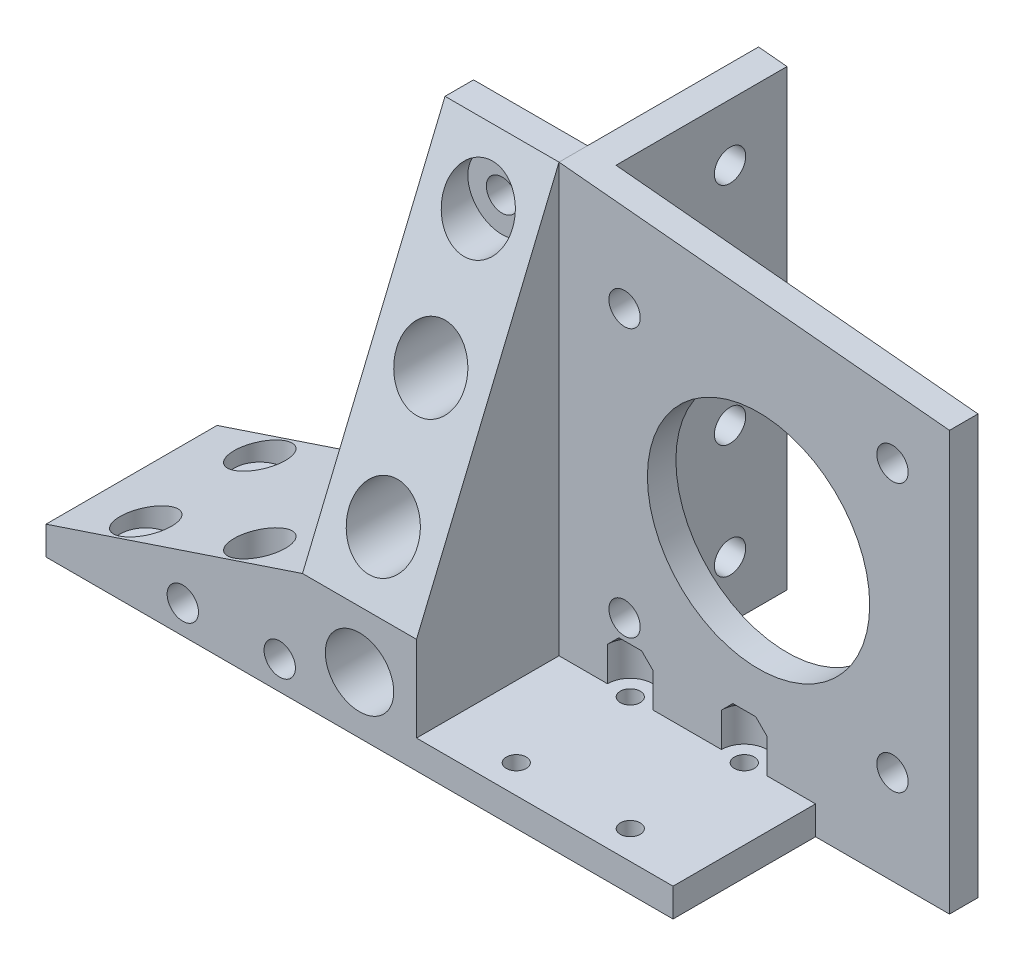
SolidWorks part; units mm, degrees
ref_plane "Plan de face" through (0, 0, 0) normal (0, 0, 1) x (1, 0, 0)
ref_plane "Plan de dessus" through (0, 0, 0) normal (0, 1, 0) x (1, 0, 0)
ref_plane "Plan de droite" through (0, 0, 0) normal (1, 0, 0) x (0, 0, -1)
sketch "Esquisse1" plane through (0, 0, 0) normal (0, 0, 1) x (1, 0, 0)
  line L1 (-9.5845, 32.7642) -> (10.4155, 32.7642)
  line L2 (-9.5845, 32.7642) -> (-9.5845, -47.2358)
  line L3 (-9.5845, -47.2358) -> (10.4155, -47.2358)
  line L4 (10.4155, 32.7642) -> (10.4155, -47.2358)
  circle A0 centre (0.4155, 22.7642) radius 2.75
  circle A1 centre (0.4155, -17.2358) radius 2.75
  circle A2 centre (0.4155, 2.7642) radius 2.75
  circle A3 centre (0.4155, -37.2358) radius 2.75
  point P13 (0.4155, -47.2358)
  dimension "D3" = 5.5
  dimension "D1" = 20
  dimension "D2" = 80
  dimension "D4" = 10
  dimension "D5" = 20
  dimension "D6" = 10
  dimension "D7" = 20
extrude "Boss.-Extru.1" add sketch "Esquisse1" along normal blind 5
sketch "Esquisse3" plane through (0, 0, 5) normal (0, 0, 1) x (1, 0, 0)
  line L0 (-9.5845, -47.2358) -> (-54.5845, -47.2358)
  line L1 (-54.5845, -47.2358) -> (-54.5845, -42.2358)
  line L2 (-54.5845, -42.2358) -> (-9.5845, -27.2358)
  line L3 (-9.5845, 32.7642) -> (-9.5845, -47.2358) construction
  line L4 (-9.5845, -27.2358) -> (-9.5845, -47.2358)
  line L5 (10.4155, -47.2358) -> (55.4155, -47.2358)
  line L6 (55.4155, -47.2358) -> (55.4155, -42.2358)
  line L7 (55.4155, -42.2358) -> (10.4155, -42.2358)
  line L8 (10.4155, -47.2358) -> (10.4155, 32.7642) construction
  line L9 (10.4155, -42.2358) -> (10.4155, -47.2358)
  dimension "D1" = 5
  dimension "D2" = 45
  dimension "D3" = 20
extrude "Boss.-Extru.2" add sketch "Esquisse3" against normal blind 5
sketch "Esquisse4" plane through (0, 0, 5) normal (0, 0, 1) x (1, 0, 0)
  line L0 (55.4155, -47.2358) -> (55.4155, -42.2358) construction
  line L1 (55.4155, -42.2358) -> (10.4155, -42.2358) construction
  line L2 (-9.5845, -27.2358) -> (-54.5845, -42.2358) construction
  line L3 (-54.5845, -42.2358) -> (-54.5845, -47.2358) construction
  line L4 (-54.5845, -47.2358) -> (55.4155, -47.2358) construction
  line L5 (55.4155, -47.2358) -> (55.4155, -42.2358)
  line L6 (55.4155, -42.2358) -> (10.4155, -42.2358)
  line L7 (-9.5845, -27.2358) -> (-54.5845, -42.2358)
  line L8 (-54.5845, -42.2358) -> (-54.5845, -47.2358)
  line L9 (-54.5845, -47.2358) -> (55.4155, -47.2358)
  line L11 (-9.5845, -27.2358) -> (10.4155, -27.2358)
  line L12 (10.4155, -42.2358) -> (10.4155, 32.7642) construction
  line L13 (10.4155, -27.2358) -> (10.4155, -42.2358)
  circle A0 centre (0.4155, -37.2358) radius 2.75 construction
  circle A1 centre (0.4155, -37.2358) radius 2.75
extrude "Boss.-Extru.3" add sketch "Esquisse4" along normal blind 25
sketch "Esquisse5" plane through (-9.5845, 0, 0) normal (-1, 0, 0) x (0, 0, 1)
  line L0 (5, -27.2358) -> (30, -27.2358)
  line L1 (30, -27.2358) -> (5, 32.7642)
  line L2 (5, 32.7642) -> (5, -27.2358)
extrude "Boss.-Extru.4" add sketch "Esquisse5" against normal up to surface (20 mm away) up to face at (10.4155, -12.2358, 11.6667)
sketch "Esquisse6" plane through (0, 0, 5) normal (0, 0, -1) x (-1, 0, 0)
  circle A0 centre (-0.4155, 2.7642) radius 6
  circle A1 centre (-0.4155, -17.2358) radius 6
  circle A2 centre (-0.4155, 22.7642) radius 6
  circle A3 centre (-0.4155, -37.2358) radius 6
  dimension "D1" = 12
extrude "Enlèv. mat.-Extru.1" cut sketch "Esquisse6" against normal up to next
sketch "Esquisse7" plane through (0, -47.2358, 0) normal (0, -1, 0) x (1, 0, 0)
  line L0 (-42.0845, 25) -> (-22.0845, 25) construction
  line L1 (-22.0845, 25) -> (-22.0845, 5) construction
  line L2 (-54.5845, 0) -> (-54.5845, 30) construction
  line L3 (22.9155, 5) -> (22.9155, 25) construction
  line L4 (22.9155, 25) -> (42.9155, 25) construction
  line L5 (55.4155, 0) -> (55.4155, 30) construction
  circle A0 centre (-42.0845, 25) radius 1.75
  circle A1 centre (-22.0845, 25) radius 1.75
  circle A2 centre (-22.0845, 5) radius 1.75
  circle A3 centre (-42.0845, 5) radius 1.75
  circle A4 centre (42.9155, 25) radius 1.75
  circle A5 centre (42.9155, 5) radius 1.75
  circle A6 centre (22.9155, 5) radius 1.75
  circle A7 centre (22.9155, 25) radius 1.75
  point P8 (-22.0845, 15)
  point P11 (-54.5845, 15)
  point P12 (-32.0845, 25)
  point P21 (22.9155, 15)
  point P24 (55.4155, 15)
  point P25 (32.9155, 25)
  dimension "D1" = 3.5
  dimension "D4" = 3.5
  dimension "D2" = 20
  dimension "D3" = 22.5
  dimension "D5" = 20
  dimension "D6" = 22.5
extrude "Enlèv. mat.-Extru.2" cut sketch "Esquisse7" against normal up to next
ref_plane "Plan3" through (0, -42.2358, 0) normal (0, -1, 0) x (-1, 0, 0)
sketch "Esquisse9" plane through (0, -42.2358, 0) normal (0, -1, 0) x (-1, 0, 0)
  circle A0 centre (42.0845, -25) radius 4.5
  circle A1 centre (22.0845, -25) radius 4.5
  circle A2 centre (22.0845, -5) radius 4.5
  circle A3 centre (42.0845, -5) radius 4.5
  dimension "D1" = 9
extrude "Enlèv. mat.-Extru.3" cut sketch "Esquisse9" against normal up to next
sketch "Esquisse11" plane through (0, 0, 0) normal (0, 0, -1) x (-1, 0, 0)
  line L0 (-10.4155, -42.2358) -> (-55.4155, -42.2358)
  line L2 (-10.4155, -42.2358) -> (-10.4155, 32.7642)
  line L3 (-10.4155, -42.2358) -> (-10.4155, 32.7642) construction
  line L4 (-10.4155, 32.7642) -> (-78.9155, 26.2642)
  line L5 (-55.4155, -42.2358) -> (-55.4155, -47.2358)
  line L6 (-55.4155, -47.2358) -> (-78.9155, -47.2358)
  line L7 (-78.9155, -47.2358) -> (-78.9155, 26.2642)
  line L8 (-68.9155, 16.2642) -> (-68.9155, -30.7358) construction
  line L9 (-68.9155, -30.7358) -> (-21.9155, -30.7358) construction
  circle A0 centre (-45.4155, -7.2358) radius 19.5
  circle A1 centre (-21.9155, 16.2642) radius 2.75
  circle A2 centre (-21.9155, -30.7358) radius 2.75
  circle A3 centre (-68.9155, -30.7358) radius 2.75
  circle A4 centre (-68.9155, 16.2642) radius 2.75
  point P22 (-45.4155, -30.7358)
  point P23 (-68.9155, -7.2358)
  dimension "D3" = 39
  dimension "D4" = 5.5
  dimension "D1" = 35
  dimension "D2" = 35
  dimension "D5" = 47
  dimension "D6" = 10
  dimension "D7" = 10
extrude "Boss.-Extru.5" add sketch "Esquisse11" against normal blind 5
sketch "Esquisse12" plane through (0, -42.2358, 0) normal (0, 1, 0) x (1, 0, 0)
  circle A0 centre (22.9155, -5) radius 4
  circle A1 centre (42.9155, -5) radius 4
  arc A2 (21.1655, -5) -> (24.6655, -5) centre (22.9155, -5) ccw construction
  arc A3 (41.1655, -5) -> (44.6655, -5) centre (42.9155, -5) ccw construction
  dimension "D1" = 8
extrude "Enlèv. mat.-Extru.5" cut sketch "Esquisse12" along normal blind 8
chamfer "Chanfrein1" distance 2 angle 45 2 edges at (42.9155, -34.2358, 1) (22.9155, -34.2358, 1)
sketch "Esquisse13" plane through (0, 0, 0) normal (0, 0, -1) x (-1, 0, 0)
  line L0 (54.5845, -47.2358) -> (-78.9155, -47.2358) construction
  line L1 (-10.4155, 32.7642) -> (-15.4155, 32.2898)
  line L2 (-10.4155, 32.7642) -> (-10.4155, -47.2358)
  line L3 (-10.4155, -47.2358) -> (-15.4155, -47.2358)
  line L4 (-15.4155, 32.2898) -> (-15.4155, -47.2358)
  line L5 (-10.4155, 32.7642) -> (-78.9155, 26.2642) construction
  dimension "D1" = 5
extrude "Boss.-Extru.6" add sketch "Esquisse13" along normal blind 30
sketch "Esquisse14" plane through (15.4155, 0, 0) normal (1, 0, 0) x (0, 0, -1)
  line L0 (30, 32.2898) -> (30, -47.2358) construction
  line L1 (30, 32.2898) -> (0, 32.2898) construction
  line L2 (30, -47.2358) -> (0, -47.2358) construction
  circle A0 centre (20, 22.2898) radius 2.75
  circle A1 centre (20, 2.2898) radius 2.75
  circle A2 centre (20, -17.2358) radius 2.75
  circle A3 centre (20, -37.2358) radius 2.75
  dimension "D3" = 5.5
  dimension "D1" = 10
  dimension "D2" = 10
  dimension "D4" = 10
  dimension "D5" = 20
  dimension "D6" = 20
extrude "Enlèv. mat.-Extru.6" cut sketch "Esquisse14" against normal up to next
sketch "Esquisse15" plane through (0, 0, 30) normal (0, 0, 1) x (1, 0, 0)
  line L0 (-54.5845, -47.2358) -> (55.4155, -47.2358) construction
  line L1 (-30.5845, -42.2358) -> (-13.5845, -42.2358) construction
  line L2 (-20.3345, -42.2358) -> (-23.8345, -42.2358) construction
  line L3 (-20.3345, -42.2358) -> (-23.8345, -42.2358) construction
  circle A0 centre (-13.5845, -42.2358) radius 2.75
  circle A1 centre (-30.5845, -42.2358) radius 2.75
  point P9 (-37.0489, -42.2358)
  point P10 (-25.7573, -42.2358)
  point P11 (-48.6623, -42.2358)
  point P12 (-22.0845, -42.2358)
  point P13 (-22.0845, -42.2358)
  dimension "D1" = 5.5
  dimension "D3" = 17
  dimension "D4" = 5
extrude "Enlèv. mat.-Extru.7" cut sketch "Esquisse15" against normal up to next
